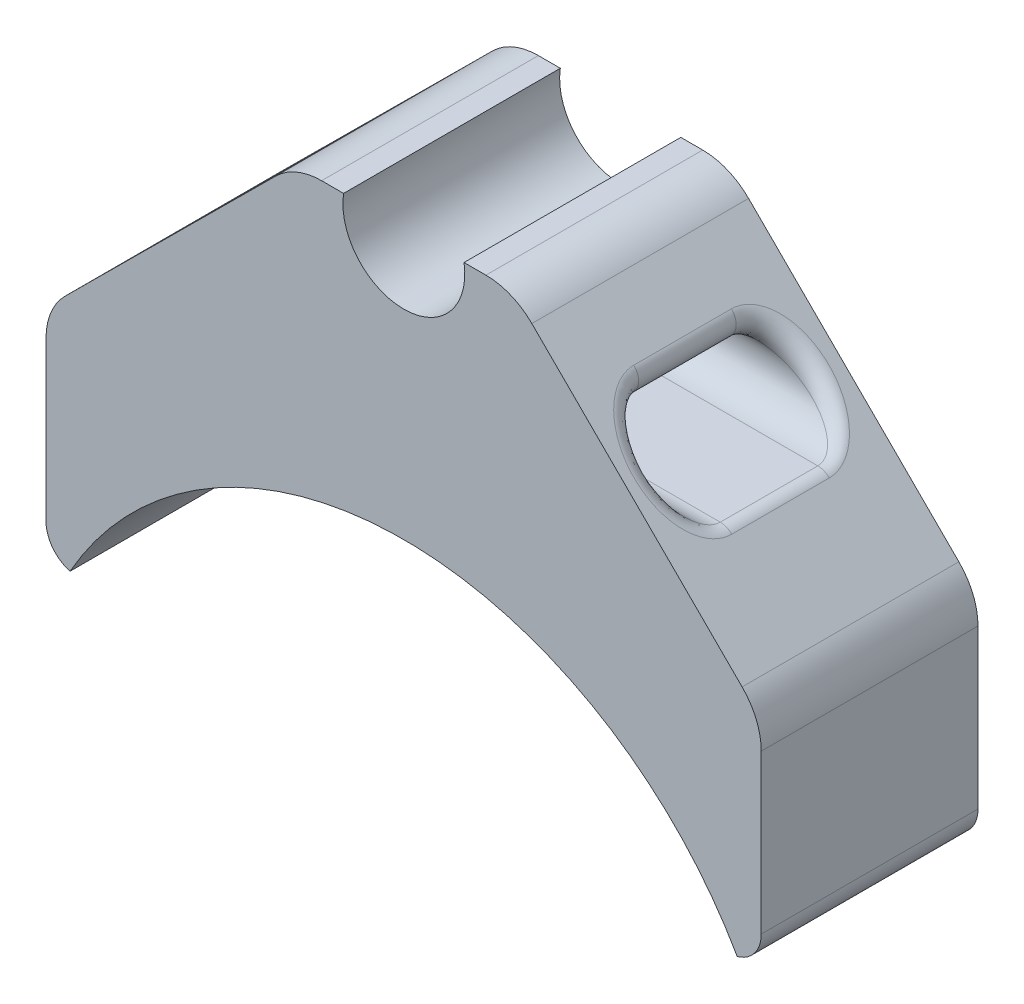
SolidWorks part; units mm, degrees
ref_plane "Front Plane" through (0, 0, 0) normal (0, 0, 1) x (1, 0, 0)
ref_plane "Top Plane" through (0, 0, 0) normal (0, 1, 0) x (1, 0, 0)
ref_plane "Right Plane" through (0, 0, 0) normal (1, 0, 0) x (0, 0, -1)
sketch "Sketch1" plane through (0, 0, 0) normal (0, 0, 1) x (1, 0, 0)
  line L0 (0, 0) -> (0, 16.9418)
  line L1 (19.4386, 36.2539) -> (23.2486, 36.2539)
  line L5 (32.6601, 36.2827) -> (36.4701, 36.2827)
  line L6 (54.0018, 0) -> (55.88, 0)
  line L7 (55.88, 0) -> (55.88, 16.9418)
  line L8 (0, 0) -> (1.8782, 0)
  line L9 (36.4701, 36.2827) -> (55.88, 16.9418)
  line L10 (19.4386, 36.2539) -> (0, 16.9418)
  arc A5 (23.2486, 36.2539) -> (32.6601, 36.2827) centre (27.9566, 35.5356) ccw
  arc A7 (1.8782, 0) -> (54.0018, 0) centre (27.94, -14.7746) cw
  dimension "D1" = 16.9418
  dimension "D2" = 4.7625
extrude "Boss-Extrude2" add sketch "Sketch1" along normal blind 16.9342 contours L6 L7 L9 L5 A5 L1 L10 L0 L8 A7
fillet "Fillet1" radius 5.08 4 edges at (0, 16.9418, 8.4671) (19.4386, 36.2539, 8.4671) (55.88, 16.9418, 8.4671) (36.4701, 36.2827, 8.4671)
fillet "Fillet2" radius 2.54 2 edges at (0, 0, 8.4671) (55.88, 0, 8.4671)
ref_plane "Plane1" through (58.42, 0, 0) normal (1, 0, 0) x (0, 0, -1)
sketch "Sketch6" plane through (58.42, 0, 0) normal (1, 0, 0) x (0, 0, -1)
  line L0 (-4.7492, 26.6983) -> (-12.3692, 26.6983) construction
  line L1 (-4.7492, 24.1583) -> (-12.3692, 24.1583)
  line L2 (-4.7492, 29.2383) -> (-12.3692, 29.2383)
  arc A0 (-4.7492, 24.1583) -> (-4.7492, 29.2383) centre (-4.7492, 26.6983) ccw
  arc A1 (-12.3692, 29.2383) -> (-12.3692, 24.1583) centre (-12.3692, 26.6983) ccw
  point P2 (-8.5592, 26.6983)
  point P7 (0, 0)
  point P8 (0, 0)
extrude "Cut-Extrude3" cut sketch "Sketch6" against normal through all both and the other way through all
fillet "Fillet3" radius 1.27 4 edges at (46.0887, 26.6983, 14.9092) (43.5396, 29.2383, 8.5592) (46.0887, 26.6983, 2.2092) (48.6377, 24.1583, 8.5592)
fillet "Fillet4" radius 1.27 4 edges at (9.8204, 26.6983, 2.2092) (7.2638, 24.1583, 8.5592) (9.8204, 26.6983, 14.9092) (12.3771, 29.2383, 8.5592)
